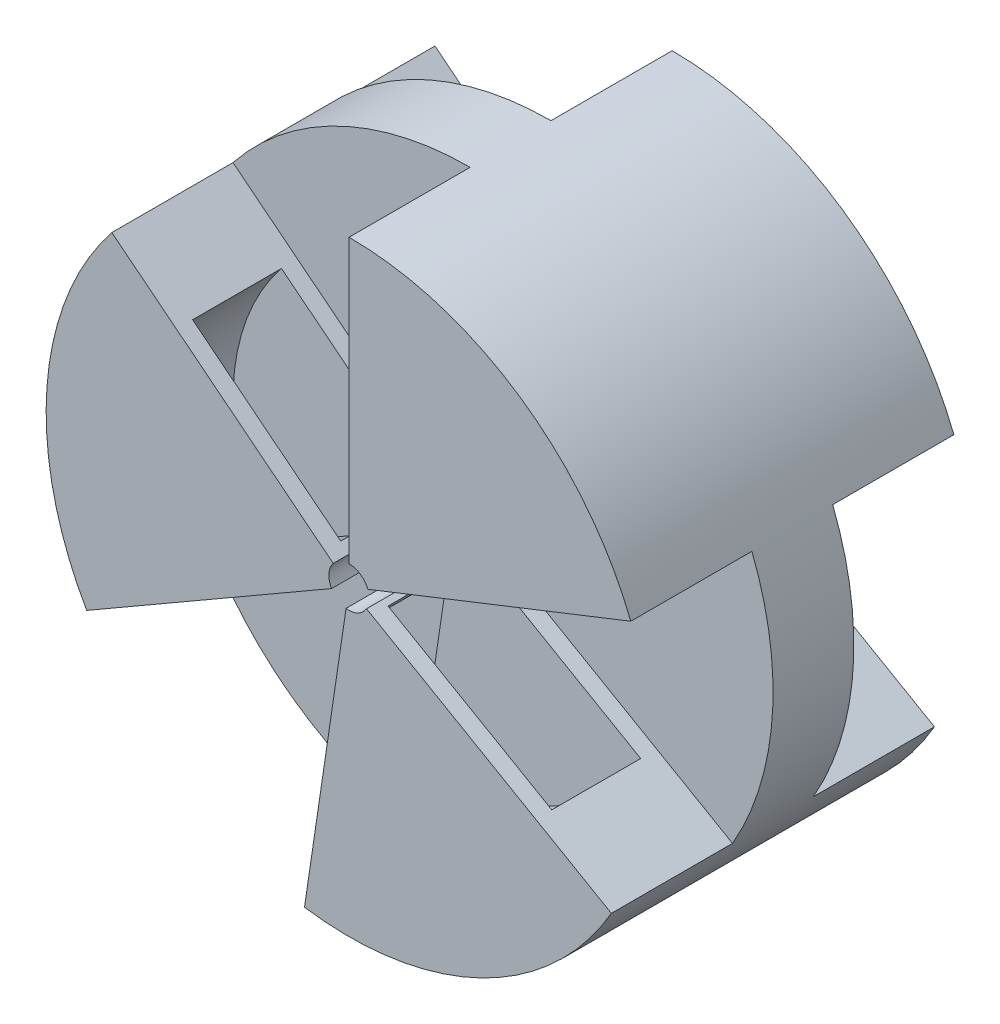
SolidWorks part; units mm, degrees
ref_plane "Plan de face" through (0, 0, 0) normal (0, 0, 1) x (1, 0, 0)
ref_plane "Plan de dessus" through (0, 0, 0) normal (0, 1, 0) x (1, 0, 0)
ref_plane "Plan de droite" through (0, 0, 0) normal (1, 0, 0) x (0, 0, -1)
sketch "Esquisse1" plane through (0, 0, 0) normal (0, 0, 1) x (1, 0, 0)
  line L0 (0, 0) -> (0, 8.0065) construction
  circle A0 centre (0, 0) radius 7.5
  circle A2 centre (0, 0) radius 4 construction
  arc A3 (0, 4) -> (3.7206, 1.4688) centre (0, 0) cw
  arc A4 (3.4641, -2) -> (-0.5883, -3.9565) centre (0, 0) cw
  arc A5 (-3.4641, -2) -> (-3.1323, 2.4877) centre (0, 0) cw
  point P14 (0, 0)
  dimension "D1" = 15
  dimension "D2" = 8
  dimension "D3" = 4.5
  dimension "D5" = 6
  dimension "D4" = 3
extrude "Boss.-Extru.1" add sketch "Esquisse1" along normal blind 1 contours A0 region at (0, 0, 0)
extrude "Extru.-Mince1" add sketch "Esquisse1<3>" against normal blind 3 thin contours A4 | A3 | A5 thin type two direction wall 3.5 second wall 3.5
sketch "Esquisse1<3>" plane through (0, 0, 0) normal (0, 0, 1) x (1, 0, 0) same geometry as "Esquisse1"
sketch "Esquisse2" plane through (0, 0, 0) normal (0, 1, 0) x (1, 0, 0)
  line L0 (-0.0735, 0.0583) -> (-0.0735, 3.5328) construction
  line L1 (-0.3915, 3) -> (-0.3915, 0) construction
  line L2 (-0.3915, 3) -> (-0.3915, 0) construction
  line L11 (-5.473, 0.4) -> (-0.7915, 0.4)
  line L12 (-0.7915, 0.4) -> (-0.7915, 2.6)
  line L13 (-0.7915, 2.6) -> (-5.473, 2.6)
  line L14 (-5.473, 2.6) -> (-5.473, 0.4)
  line L15 (-5.473, 0.4) -> (-0.7915, 0.4)
  line L16 (-0.7915, 0.4) -> (-0.7915, 2.6)
  line L17 (-0.7915, 2.6) -> (-5.473, 2.6)
  line L18 (-5.473, 2.6) -> (-5.473, 0.4)
  circle A0 centre (-4.0735, 1.5) radius 0.5 construction
  point P7 (-0.3915, 1.5)
  dimension "D1" = 1
  dimension "D2" = 4
  dimension "D3" = 0.4
revolve "Enlèvement de matière-Révolution1" cut sketch "Esquisse2" angle 360 about L0
mirror "Symétrie1" about plane through (0, 0, 1) normal (0, 0, 1) of "Enlèvement de matière-Révolution1", "Boss.-Extru.1", "Extru.-Mince1"
